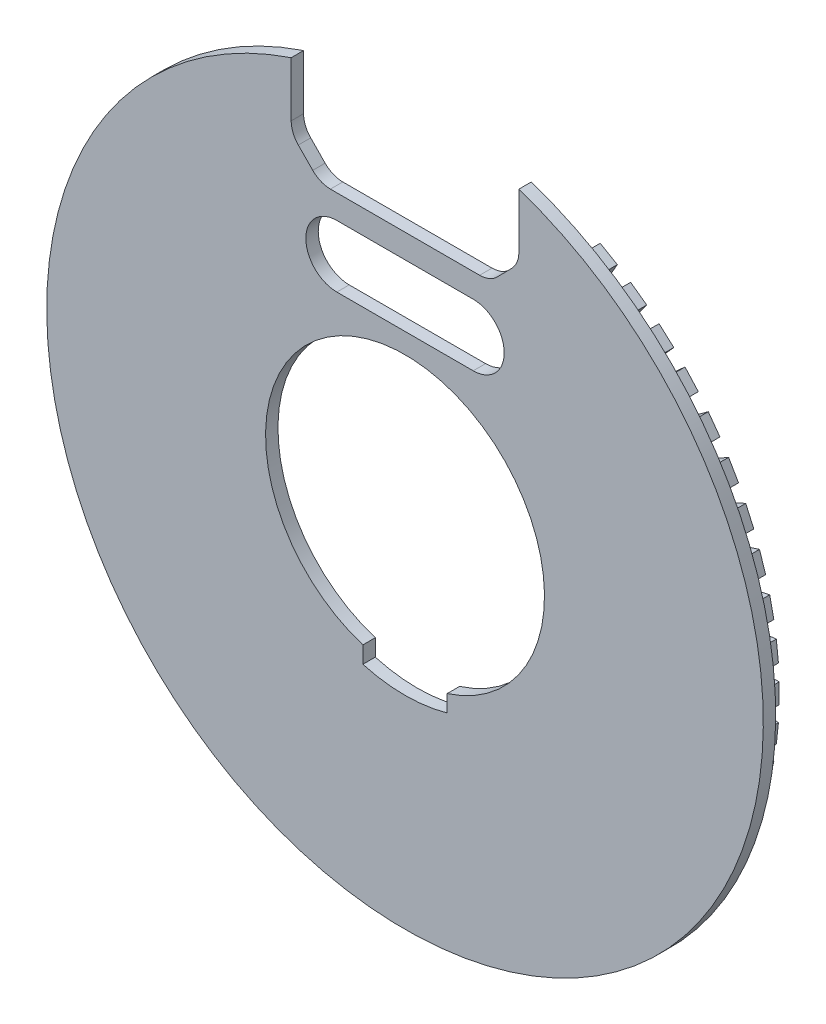
SolidWorks part; units mm, degrees
ref_plane "Front Plane" through (0, 0, 0) normal (0, 0, 1) x (1, 0, 0)
ref_plane "Top Plane" through (0, 0, 0) normal (0, 1, 0) x (1, 0, 0)
ref_plane "Right Plane" through (0, 0, 0) normal (1, 0, 0) x (0, 0, -1)
ref_axis "Axis1" through (0, 0, 54.6575) along (0, 0, -1)
sketch "Sketch1" plane through (0, 0, 0) normal (0, 0, 1) x (1, 0, 0)
  line L12 (20.9871, 19.8336) -> (20.5267, 19.3732)
  line L14 (27.041, 8.0901) -> (27.67, 8.2586)
  line L16 (-27.67, 8.2586) -> (-27.041, 8.0901)
  line L21 (-20.5267, 19.3732) -> (-20.9871, 19.8336)
  line L72 (-4.297, -11.3403) -> (-4.297, -10.3637)
  line L89 (4.297, -11.3403) -> (4.297, -10.3637)
  line L92 (4.297, -11.3403) -> (4.297, -10.3637)
  line L93 (-4.297, -11.3403) -> (-4.297, -10.3637)
  line L100 (-10.7726, 3.134) -> (-10.6892, 3.0858)
  line L101 (-8.017, 7.7142) -> (-8.1004, 7.7623)
  line L102 (-8.1004, -7.7623) -> (-8.017, -7.7142)
  line L103 (-10.6892, -3.0858) -> (-10.7726, -3.134)
  line L104 (10.7726, -3.134) -> (10.6892, -3.0858)
  line L105 (8.017, -7.7142) -> (8.1004, -7.7623)
  line L120 (8.1004, 7.7623) -> (8.017, 7.7142)
  line L121 (10.6892, 3.0858) -> (10.7726, 3.134)
  line L122 (-2.6722, 10.8963) -> (-2.6722, 10.8)
  line L123 (2.6722, 10.8) -> (2.6722, 10.8963)
  line L196 (6.6828, -28.0922) -> (6.5143, -27.4632)
  line L197 (-6.5143, -27.4632) -> (-6.6828, -28.0922)
  line L206 (2.6722, -12.1691) -> (2.6722, -10.8)
  line L207 (-2.6722, -10.8) -> (-2.6722, -12.1691)
  line L210 (27.154, -15.4668) -> (26.9697, -15.2479)
  line L211 (28.01, -13.2402) -> (28.2951, -13.2646)
  line L212 (24.7951, -19.0202) -> (24.6422, -18.7783)
  line L213 (25.9462, -16.931) -> (26.2253, -16.9939)
  line L214 (29.0072, -11.6252) -> (28.7947, -11.4335)
  line L216 (29.552, -9.3029) -> (29.8377, -9.2883)
  line L229 (30.32, -7.5671) -> (30.0834, -7.4061)
  line L230 (30.5435, -5.1923) -> (30.8246, -5.1388)
  line L231 (31.068, -3.3681) -> (30.8117, -3.2408)
  line L232 (30.966, -0.9849) -> (31.2372, -0.8937)
  line L233 (31.2372, 0.8937) -> (30.966, 0.9849)
  line L234 (30.8117, 3.2408) -> (31.068, 3.3681)
  line L235 (30.8246, 5.1388) -> (30.5435, 5.1923)
  line L238 (30.0834, 7.4061) -> (30.32, 7.5671)
  line L239 (29.8377, 9.2883) -> (29.552, 9.3029)
  line L240 (28.7947, 11.4335) -> (29.0072, 11.6252)
  line L241 (-11.3028, 29.1343) -> (-11.2979, 28.8482)
  line L242 (-13.3719, 27.9474) -> (-13.5777, 28.1462)
  line L243 (-15.1646, 27.3239) -> (-15.1208, 27.0411)
  line L244 (-17.0528, 25.8663) -> (-17.2838, 26.0352)
  line L245 (17.2838, 26.0352) -> (17.0528, 25.8663)
  line L246 (15.1208, 27.0411) -> (15.1646, 27.3239)
  line L247 (13.5777, 28.1462) -> (13.3719, 27.9474)
  line L248 (11.2979, 28.8482) -> (11.3028, 29.1343)
  line L249 (26.2253, 16.9939) -> (25.9462, 16.931)
  line L250 (24.6422, 18.7783) -> (24.7951, 19.0202)
  line L251 (28.2951, 13.2646) -> (28.01, 13.2402)
  line L252 (26.9697, 15.2479) -> (27.154, 15.4668)
  line L253 (20.6679, 23.4393) -> (20.4161, 23.3033)
  line L254 (18.6621, 24.7303) -> (18.744, 25.0045)
  line L255 (23.6671, 20.4067) -> (23.3991, 20.3063)
  line L256 (21.8557, 21.9588) -> (21.9742, 22.2193)
  line L257 (-24.7951, 19.0202) -> (-24.6422, 18.7783)
  line L258 (-25.9462, 16.931) -> (-26.2253, 16.9939)
  line L259 (-27.154, 15.4668) -> (-26.9697, 15.2479)
  line L260 (-28.01, 13.2402) -> (-28.2951, 13.2646)
  line L261 (-18.744, 25.0045) -> (-18.6621, 24.7303)
  line L262 (-20.4161, 23.3033) -> (-20.6679, 23.4393)
  line L263 (-21.9742, 22.2193) -> (-21.8557, 21.9588)
  line L264 (-23.3991, 20.3063) -> (-23.6671, 20.4067)
  line L265 (-29.0072, 11.6252) -> (-28.7947, 11.4335)
  line L266 (-29.552, 9.3029) -> (-29.8377, 9.2883)
  line L267 (-30.32, 7.5671) -> (-30.0834, 7.4061)
  line L268 (-30.5435, 5.1923) -> (-30.8246, 5.1388)
  line L269 (-31.068, 3.3681) -> (-30.8117, 3.2408)
  line L270 (-30.966, 0.9849) -> (-31.2372, 0.8937)
  line L271 (-31.2372, -0.8937) -> (-30.966, -0.9849)
  line L272 (-30.8117, -3.2408) -> (-31.068, -3.3681)
  line L273 (-20.6679, -23.4393) -> (-20.4161, -23.3033)
  line L274 (-18.6621, -24.7303) -> (-18.744, -25.0045)
  line L275 (-23.6671, -20.4067) -> (-23.3991, -20.3063)
  line L276 (-21.8557, -21.9588) -> (-21.9742, -22.2193)
  line L277 (-13.5777, -28.1462) -> (-13.3719, -27.9474)
  line L278 (-11.2979, -28.8482) -> (-11.3028, -29.1343)
  line L279 (-17.2838, -26.0352) -> (-17.0528, -25.8663)
  line L280 (-15.1208, -27.0411) -> (-15.1646, -27.3239)
  line L281 (-28.2951, -13.2646) -> (-28.01, -13.2402)
  line L282 (-26.9697, -15.2479) -> (-27.154, -15.4668)
  line L283 (-26.2253, -16.9939) -> (-25.9462, -16.931)
  line L284 (-24.6422, -18.7783) -> (-24.7951, -19.0202)
  line L285 (-29.8377, -9.2883) -> (-29.552, -9.3029)
  line L286 (-28.7947, -11.4335) -> (-29.0072, -11.6252)
  line L287 (-30.8246, -5.1388) -> (-30.5435, -5.1923)
  line L288 (-30.0834, -7.4061) -> (-30.32, -7.5671)
  line L289 (15.1646, -27.3239) -> (15.1208, -27.0411)
  line L290 (17.0528, -25.8663) -> (17.2838, -26.0352)
  line L291 (11.3028, -29.1343) -> (11.2979, -28.8482)
  line L292 (13.3719, -27.9474) -> (13.5777, -28.1462)
  line L293 (21.9742, -22.2193) -> (21.8557, -21.9588)
  line L294 (23.3991, -20.3063) -> (23.6671, -20.4067)
  line L295 (18.744, -25.0045) -> (18.6621, -24.7303)
  line L296 (20.4161, -23.3033) -> (20.6679, -23.4393)
  line L297 (-9.6186, -29.7329) -> (-9.4418, -29.5079)
  line L298 (-7.2645, -30.1179) -> (-7.2304, -30.402)
  line L299 (7.2304, -30.402) -> (7.2645, -30.1179)
  line L300 (9.4418, -29.5079) -> (9.6186, -29.7329)
  line L301 (-7.0878, 20.754) -> (-8.2524, 21.9387)
  line L302 (8.2524, 21.9387) -> (7.0878, 20.754)
  line L303 (-8.6826, 26.4576) -> (-8.6826, 22.9901)
  line L304 (8.6826, 26.4576) -> (8.6826, 22.9901)
  line L305 (4.4477, 24.65) -> (4.4477, 31.5861)
  line L306 (-4.4477, 31.5861) -> (-4.4477, 24.65)
  line L307 (4.5426, 32.95) -> (4.5426, 31.81)
  line L308 (-4.5426, 31.81) -> (-4.5426, 32.95)
  line L309 (-6.1155, 33.25) -> (-5.0016, 33.25)
  line L310 (5.0016, 33.25) -> (6.1155, 33.25)
  line L311 (6.0182, 20.3056) -> (-6.0182, 20.3056)
  line L312 (6.0182, 20.3056) -> (-6.0182, 20.3056)
  line L313 (5.0016, 33.25) -> (6.1155, 33.25)
  line L314 (-6.1155, 33.25) -> (-5.0016, 33.25)
  line L315 (-4.5426, 31.81) -> (-4.5426, 32.95)
  line L316 (4.5426, 32.95) -> (4.5426, 31.81)
  line L317 (-4.4477, 31.5861) -> (-4.4477, 24.65)
  line L318 (4.4477, 24.65) -> (4.4477, 31.5861)
  line L319 (8.6826, 26.4576) -> (8.6826, 22.9901)
  line L320 (-8.6826, 26.4576) -> (-8.6826, 22.9901)
  line L321 (8.2524, 21.9387) -> (7.0878, 20.754)
  line L322 (-7.0878, 20.754) -> (-8.2524, 21.9387)
  line L323 (9.4418, -29.5079) -> (9.6186, -29.7329)
  line L324 (7.2304, -30.402) -> (7.2645, -30.1179)
  line L325 (-7.2645, -30.1179) -> (-7.2304, -30.402)
  line L326 (-9.6186, -29.7329) -> (-9.4418, -29.5079)
  line L327 (20.4161, -23.3033) -> (20.6679, -23.4393)
  line L328 (18.744, -25.0045) -> (18.6621, -24.7303)
  line L329 (23.3991, -20.3063) -> (23.6671, -20.4067)
  line L330 (21.9742, -22.2193) -> (21.8557, -21.9588)
  line L331 (13.3719, -27.9474) -> (13.5777, -28.1462)
  line L332 (11.3028, -29.1343) -> (11.2979, -28.8482)
  line L333 (17.0528, -25.8663) -> (17.2838, -26.0352)
  line L334 (15.1646, -27.3239) -> (15.1208, -27.0411)
  line L335 (-30.0834, -7.4061) -> (-30.32, -7.5671)
  line L336 (-30.8246, -5.1388) -> (-30.5435, -5.1923)
  line L337 (-28.7947, -11.4335) -> (-29.0072, -11.6252)
  line L338 (-29.8377, -9.2883) -> (-29.552, -9.3029)
  line L339 (-24.6422, -18.7783) -> (-24.7951, -19.0202)
  line L340 (-26.2253, -16.9939) -> (-25.9462, -16.931)
  line L341 (-26.9697, -15.2479) -> (-27.154, -15.4668)
  line L342 (-28.2951, -13.2646) -> (-28.01, -13.2402)
  line L343 (-15.1208, -27.0411) -> (-15.1646, -27.3239)
  line L344 (-17.2838, -26.0352) -> (-17.0528, -25.8663)
  line L345 (-11.2979, -28.8482) -> (-11.3028, -29.1343)
  line L346 (-13.5777, -28.1462) -> (-13.3719, -27.9474)
  line L347 (-21.8557, -21.9588) -> (-21.9742, -22.2193)
  line L348 (-23.6671, -20.4067) -> (-23.3991, -20.3063)
  line L349 (-18.6621, -24.7303) -> (-18.744, -25.0045)
  line L350 (-20.6679, -23.4393) -> (-20.4161, -23.3033)
  line L351 (-30.8117, -3.2408) -> (-31.068, -3.3681)
  line L352 (-31.2372, -0.8937) -> (-30.966, -0.9849)
  line L353 (-30.966, 0.9849) -> (-31.2372, 0.8937)
  line L354 (-31.068, 3.3681) -> (-30.8117, 3.2408)
  line L355 (-30.5435, 5.1923) -> (-30.8246, 5.1388)
  line L356 (-30.32, 7.5671) -> (-30.0834, 7.4061)
  line L357 (-29.552, 9.3029) -> (-29.8377, 9.2883)
  line L358 (-29.0072, 11.6252) -> (-28.7947, 11.4335)
  line L359 (-23.3991, 20.3063) -> (-23.6671, 20.4067)
  line L360 (-21.9742, 22.2193) -> (-21.8557, 21.9588)
  line L361 (-20.4161, 23.3033) -> (-20.6679, 23.4393)
  line L362 (-18.744, 25.0045) -> (-18.6621, 24.7303)
  line L363 (-28.01, 13.2402) -> (-28.2951, 13.2646)
  line L364 (-27.154, 15.4668) -> (-26.9697, 15.2479)
  line L365 (-25.9462, 16.931) -> (-26.2253, 16.9939)
  line L366 (-24.7951, 19.0202) -> (-24.6422, 18.7783)
  line L367 (21.8557, 21.9588) -> (21.9742, 22.2193)
  line L368 (23.6671, 20.4067) -> (23.3991, 20.3063)
  line L369 (18.6621, 24.7303) -> (18.744, 25.0045)
  line L370 (20.6679, 23.4393) -> (20.4161, 23.3033)
  line L371 (26.9697, 15.2479) -> (27.154, 15.4668)
  line L372 (28.2951, 13.2646) -> (28.01, 13.2402)
  line L373 (24.6422, 18.7783) -> (24.7951, 19.0202)
  line L374 (26.2253, 16.9939) -> (25.9462, 16.931)
  line L375 (11.2979, 28.8482) -> (11.3028, 29.1343)
  line L376 (13.5777, 28.1462) -> (13.3719, 27.9474)
  line L377 (15.1208, 27.0411) -> (15.1646, 27.3239)
  line L378 (17.2838, 26.0352) -> (17.0528, 25.8663)
  line L379 (-17.0528, 25.8663) -> (-17.2838, 26.0352)
  line L380 (-15.1646, 27.3239) -> (-15.1208, 27.0411)
  line L381 (-13.3719, 27.9474) -> (-13.5777, 28.1462)
  line L382 (-11.3028, 29.1343) -> (-11.2979, 28.8482)
  line L383 (28.7947, 11.4335) -> (29.0072, 11.6252)
  line L384 (29.8377, 9.2883) -> (29.552, 9.3029)
  line L385 (30.0834, 7.4061) -> (30.32, 7.5671)
  line L386 (30.8246, 5.1388) -> (30.5435, 5.1923)
  line L387 (30.8117, 3.2408) -> (31.068, 3.3681)
  line L388 (31.2372, 0.8937) -> (30.966, 0.9849)
  line L389 (30.966, -0.9849) -> (31.2372, -0.8937)
  line L390 (31.068, -3.3681) -> (30.8117, -3.2408)
  line L391 (30.5435, -5.1923) -> (30.8246, -5.1388)
  line L392 (30.32, -7.5671) -> (30.0834, -7.4061)
  line L393 (29.552, -9.3029) -> (29.8377, -9.2883)
  line L394 (29.0072, -11.6252) -> (28.7947, -11.4335)
  line L395 (25.9462, -16.931) -> (26.2253, -16.9939)
  line L396 (24.7951, -19.0202) -> (24.6422, -18.7783)
  line L397 (28.01, -13.2402) -> (28.2951, -13.2646)
  line L398 (27.154, -15.4668) -> (26.9697, -15.2479)
  line L420 (-2.6722, -10.8) -> (-2.6722, -12.1691)
  line L421 (2.6722, -12.1691) -> (2.6722, -10.8)
  line L430 (2.6722, 10.8) -> (2.6722, 10.8963)
  line L431 (-2.6722, 10.8963) -> (-2.6722, 10.8)
  line L432 (10.6892, 3.0858) -> (10.7726, 3.134)
  line L433 (8.1004, 7.7623) -> (8.017, 7.7142)
  line L434 (8.017, -7.7142) -> (8.1004, -7.7623)
  line L435 (10.7726, -3.134) -> (10.6892, -3.0858)
  line L436 (-10.6892, -3.0858) -> (-10.7726, -3.134)
  line L437 (-8.1004, -7.7623) -> (-8.017, -7.7142)
  line L438 (-8.017, 7.7142) -> (-8.1004, 7.7623)
  line L439 (-10.7726, 3.134) -> (-10.6892, 3.0858)
  line L510 (-6.5143, -27.4632) -> (-6.6828, -28.0922)
  line L511 (6.6828, -28.0922) -> (6.5143, -27.4632)
  line L512 (-20.5267, 19.3732) -> (-20.9871, 19.8336)
  line L513 (-27.67, 8.2586) -> (-27.041, 8.0901)
  line L514 (27.041, 8.0901) -> (27.67, 8.2586)
  line L515 (20.9871, 19.8336) -> (20.5267, 19.3732)
  arc A18 (27.67, 8.2586) -> (20.9871, 19.8336) centre (0, 0) ccw
  arc A80 (-3.9559, -11.8144) -> (-2.6722, -12.1691) centre (0, 0) ccw
  arc A82 (-3.9559, -11.8144) -> (-2.6722, -12.1691) centre (0, 0) ccw
  arc A149 (27.041, 8.0901) -> (20.5267, 19.3732) centre (0, 0) ccw
  arc A153 (-20.9871, 19.8336) -> (-27.67, 8.2586) centre (0, 0) ccw
  arc A162 (-20.5267, 19.3732) -> (-27.041, 8.0901) centre (0, 0) ccw
  arc A163 (-6.6828, -28.0922) -> (6.6828, -28.0922) centre (0, 0) ccw
  arc A164 (-6.5143, -27.4632) -> (6.5143, -27.4632) centre (0, 0) ccw
  arc A211 (2.6722, -10.8) -> (-2.6722, -10.8) centre (0, -10.8) ccw
  arc A217 (2.6722, -12.1691) -> (3.9559, -11.8144) centre (0, 0) ccw
  arc A225 (2.6722, -12.1691) -> (3.9559, -11.8144) centre (0, 0) ccw
  arc A226 (2.6722, -10.8) -> (-2.6722, -10.8) centre (0, -10.8) ccw
  arc A257 (-10.6892, 3.0858) -> (-8.017, 7.7142) centre (-9.3531, 5.4) ccw
  arc A258 (-8.017, -7.7142) -> (-10.6892, -3.0858) centre (-9.3531, -5.4) ccw
  arc A260 (10.6892, -3.0858) -> (8.017, -7.7142) centre (9.3531, -5.4) ccw
  arc A261 (8.017, 7.7142) -> (10.6892, 3.0858) centre (9.3531, 5.4) ccw
  arc A262 (-2.6722, 10.8) -> (2.6722, 10.8) centre (0, 10.8) ccw
  arc A263 (26.9697, -15.2479) -> (28.01, -13.2402) centre (0, 0) ccw
  arc A264 (24.6422, -18.7783) -> (25.9462, -16.931) centre (0, 0) ccw
  arc A265 (28.7947, -11.4335) -> (29.552, -9.3029) centre (0, 0) ccw
  arc A266 (30.0834, -7.4061) -> (30.5435, -5.1923) centre (0, 0) ccw
  arc A267 (30.8117, -3.2408) -> (30.966, -0.9849) centre (0, 0) ccw
  arc A268 (30.966, 0.9849) -> (30.8117, 3.2408) centre (0, 0) ccw
  arc A269 (30.5435, 5.1923) -> (30.0834, 7.4061) centre (0, 0) ccw
  arc A270 (29.552, 9.3029) -> (28.7947, 11.4335) centre (0, 0) ccw
  arc A271 (-11.2979, 28.8482) -> (-13.3719, 27.9474) centre (0, 0) ccw
  arc A272 (-15.1208, 27.0411) -> (-17.0528, 25.8663) centre (0, 0) ccw
  arc A273 (17.0528, 25.8663) -> (15.1208, 27.0411) centre (0, 0) ccw
  arc A274 (13.3719, 27.9474) -> (11.2979, 28.8482) centre (0, 0) ccw
  arc A275 (25.9462, 16.931) -> (24.6422, 18.7783) centre (0, 0) ccw
  arc A276 (28.01, 13.2402) -> (26.9697, 15.2479) centre (0, 0) ccw
  arc A277 (20.4161, 23.3033) -> (18.6621, 24.7303) centre (0, 0) ccw
  arc A278 (23.3991, 20.3063) -> (21.8557, 21.9588) centre (0, 0) ccw
  arc A279 (-24.6422, 18.7783) -> (-25.9462, 16.931) centre (0, 0) ccw
  arc A280 (-26.9697, 15.2479) -> (-28.01, 13.2402) centre (0, 0) ccw
  arc A281 (-18.6621, 24.7303) -> (-20.4161, 23.3033) centre (0, 0) ccw
  arc A283 (-21.8557, 21.9588) -> (-23.3991, 20.3063) centre (0, 0) ccw
  arc A284 (-28.7947, 11.4335) -> (-29.552, 9.3029) centre (0, 0) ccw
  arc A285 (-30.0834, 7.4061) -> (-30.5435, 5.1923) centre (0, 0) ccw
  arc A286 (-30.8117, 3.2408) -> (-30.966, 0.9849) centre (0, 0) ccw
  arc A287 (-30.966, -0.9849) -> (-30.8117, -3.2408) centre (0, 0) ccw
  arc A288 (-20.4161, -23.3033) -> (-18.6621, -24.7303) centre (0, 0) ccw
  arc A289 (-23.3991, -20.3063) -> (-21.8557, -21.9588) centre (0, 0) ccw
  arc A290 (-13.3719, -27.9474) -> (-11.2979, -28.8482) centre (0, 0) ccw
  arc A291 (-17.0528, -25.8663) -> (-15.1208, -27.0411) centre (0, 0) ccw
  arc A292 (-28.01, -13.2402) -> (-26.9697, -15.2479) centre (0, 0) ccw
  arc A293 (-25.9462, -16.931) -> (-24.6422, -18.7783) centre (0, 0) ccw
  arc A294 (-29.552, -9.3029) -> (-28.7947, -11.4335) centre (0, 0) ccw
  arc A295 (-30.5435, -5.1923) -> (-30.0834, -7.4061) centre (0, 0) ccw
  arc A296 (15.1208, -27.0411) -> (17.0528, -25.8663) centre (0, 0) ccw
  arc A297 (11.2979, -28.8482) -> (13.3719, -27.9474) centre (0, 0) ccw
  arc A298 (21.8557, -21.9588) -> (23.3991, -20.3063) centre (0, 0) ccw
  arc A299 (18.6621, -24.7303) -> (20.4161, -23.3033) centre (0, 0) ccw
  arc A300 (-9.4418, -29.5079) -> (-7.2645, -30.1179) centre (0, 0) ccw
  arc A301 (7.2645, -30.1179) -> (9.4418, -29.5079) centre (0, 0) ccw
  circle A302 centre (0, 0) radius 5
  arc A385 (9.6186, -29.7329) -> (11.3028, -29.1343) centre (0, 0) ccw
  arc A389 (7.2598, -28.2558) -> (28.1002, 7.8407) centre (0, 0) ccw
  arc A390 (-7.2304, -30.402) -> (7.2304, -30.402) centre (0, 0) ccw
  arc A391 (20.6679, -23.4393) -> (21.9742, -22.2193) centre (0, 0) ccw
  arc A392 (23.6671, -20.4067) -> (24.7951, -19.0202) centre (0, 0) ccw
  arc A393 (13.5777, -28.1462) -> (15.1646, -27.3239) centre (0, 0) ccw
  arc A394 (17.2838, -26.0352) -> (18.744, -25.0045) centre (0, 0) ccw
  arc A395 (-30.32, -7.5671) -> (-29.8377, -9.2883) centre (0, 0) ccw
  arc A396 (-29.0072, -11.6252) -> (-28.2951, -13.2646) centre (0, 0) ccw
  arc A397 (-24.7951, -19.0202) -> (-23.6671, -20.4067) centre (0, 0) ccw
  arc A398 (-27.154, -15.4668) -> (-26.2253, -16.9939) centre (0, 0) ccw
  arc A399 (-15.1646, -27.3239) -> (-13.5777, -28.1462) centre (0, 0) ccw
  arc A400 (-11.3028, -29.1343) -> (-9.6186, -29.7329) centre (0, 0) ccw
  arc A401 (-21.9742, -22.2193) -> (-20.6679, -23.4393) centre (0, 0) ccw
  arc A402 (-18.744, -25.0045) -> (-17.2838, -26.0352) centre (0, 0) ccw
  arc A403 (-31.068, -3.3681) -> (-30.8246, -5.1388) centre (0, 0) ccw
  arc A404 (-31.2372, 0.8937) -> (-31.2372, -0.8937) centre (0, 0) ccw
  arc A405 (-30.8246, 5.1388) -> (-31.068, 3.3681) centre (0, 0) ccw
  arc A406 (-29.8377, 9.2883) -> (-30.32, 7.5671) centre (0, 0) ccw
  arc A407 (-23.6671, 20.4067) -> (-24.7951, 19.0202) centre (0, 0) ccw
  arc A408 (-20.6679, 23.4393) -> (-21.9742, 22.2193) centre (0, 0) ccw
  arc A409 (-28.2951, 13.2646) -> (-29.0072, 11.6252) centre (0, 0) ccw
  arc A410 (-26.2253, 16.9939) -> (-27.154, 15.4668) centre (0, 0) ccw
  arc A411 (21.9742, 22.2193) -> (20.6679, 23.4393) centre (0, 0) ccw
  arc A412 (18.744, 25.0045) -> (17.2838, 26.0352) centre (0, 0) ccw
  arc A413 (27.154, 15.4668) -> (26.2253, 16.9939) centre (0, 0) ccw
  arc A414 (24.7951, 19.0202) -> (23.6671, 20.4067) centre (0, 0) ccw
  arc A415 (-9.2957, 29.8354) -> (-11.3028, 29.1343) centre (0, 0) ccw
  arc A416 (11.3028, 29.1343) -> (9.2957, 29.8354) centre (0, 0) ccw
  arc A417 (15.1646, 27.3239) -> (13.5777, 28.1462) centre (0, 0) ccw
  arc A418 (-17.2838, 26.0352) -> (-18.744, 25.0045) centre (0, 0) ccw
  arc A419 (-13.5777, 28.1462) -> (-15.1646, 27.3239) centre (0, 0) ccw
  arc A420 (29.0072, 11.6252) -> (28.2951, 13.2646) centre (0, 0) ccw
  arc A421 (30.32, 7.5671) -> (29.8377, 9.2883) centre (0, 0) ccw
  arc A422 (31.068, 3.3681) -> (30.8246, 5.1388) centre (0, 0) ccw
  arc A423 (31.2372, -0.8937) -> (31.2372, 0.8937) centre (0, 0) ccw
  arc A424 (30.8246, -5.1388) -> (31.068, -3.3681) centre (0, 0) ccw
  arc A425 (29.8377, -9.2883) -> (30.32, -7.5671) centre (0, 0) ccw
  arc A426 (26.2253, -16.9939) -> (27.154, -15.4668) centre (0, 0) ccw
  arc A427 (28.2951, -13.2646) -> (29.0072, -11.6252) centre (0, 0) ccw
  arc A439 (10.7726, -3.134) -> (10.7726, 3.134) centre (0, 0) ccw
  arc A440 (10.7726, -3.134) -> (10.7726, 3.134) centre (0, 0) ccw
  arc A452 (28.2951, -13.2646) -> (29.0072, -11.6252) centre (0, 0) ccw
  arc A453 (26.2253, -16.9939) -> (27.154, -15.4668) centre (0, 0) ccw
  arc A454 (29.8377, -9.2883) -> (30.32, -7.5671) centre (0, 0) ccw
  arc A455 (30.8246, -5.1388) -> (31.068, -3.3681) centre (0, 0) ccw
  arc A456 (31.2372, -0.8937) -> (31.2372, 0.8937) centre (0, 0) ccw
  arc A457 (31.068, 3.3681) -> (30.8246, 5.1388) centre (0, 0) ccw
  arc A458 (30.32, 7.5671) -> (29.8377, 9.2883) centre (0, 0) ccw
  arc A459 (29.0072, 11.6252) -> (28.2951, 13.2646) centre (0, 0) ccw
  arc A460 (-13.5777, 28.1462) -> (-15.1646, 27.3239) centre (0, 0) ccw
  arc A461 (-17.2838, 26.0352) -> (-18.744, 25.0045) centre (0, 0) ccw
  arc A462 (15.1646, 27.3239) -> (13.5777, 28.1462) centre (0, 0) ccw
  arc A463 (11.3028, 29.1343) -> (9.2957, 29.8354) centre (0, 0) ccw
  arc A464 (-9.2957, 29.8354) -> (-11.3028, 29.1343) centre (0, 0) ccw
  arc A465 (24.7951, 19.0202) -> (23.6671, 20.4067) centre (0, 0) ccw
  arc A466 (27.154, 15.4668) -> (26.2253, 16.9939) centre (0, 0) ccw
  arc A467 (18.744, 25.0045) -> (17.2838, 26.0352) centre (0, 0) ccw
  arc A468 (21.9742, 22.2193) -> (20.6679, 23.4393) centre (0, 0) ccw
  arc A469 (-26.2253, 16.9939) -> (-27.154, 15.4668) centre (0, 0) ccw
  arc A470 (-28.2951, 13.2646) -> (-29.0072, 11.6252) centre (0, 0) ccw
  arc A471 (-20.6679, 23.4393) -> (-21.9742, 22.2193) centre (0, 0) ccw
  arc A472 (-23.6671, 20.4067) -> (-24.7951, 19.0202) centre (0, 0) ccw
  arc A473 (-29.8377, 9.2883) -> (-30.32, 7.5671) centre (0, 0) ccw
  arc A474 (-30.8246, 5.1388) -> (-31.068, 3.3681) centre (0, 0) ccw
  arc A475 (-31.2372, 0.8937) -> (-31.2372, -0.8937) centre (0, 0) ccw
  arc A476 (-31.068, -3.3681) -> (-30.8246, -5.1388) centre (0, 0) ccw
  arc A477 (-18.744, -25.0045) -> (-17.2838, -26.0352) centre (0, 0) ccw
  arc A478 (-21.9742, -22.2193) -> (-20.6679, -23.4393) centre (0, 0) ccw
  arc A479 (-11.3028, -29.1343) -> (-9.6186, -29.7329) centre (0, 0) ccw
  arc A480 (-15.1646, -27.3239) -> (-13.5777, -28.1462) centre (0, 0) ccw
  arc A481 (-27.154, -15.4668) -> (-26.2253, -16.9939) centre (0, 0) ccw
  arc A482 (-24.7951, -19.0202) -> (-23.6671, -20.4067) centre (0, 0) ccw
  arc A483 (-29.0072, -11.6252) -> (-28.2951, -13.2646) centre (0, 0) ccw
  arc A484 (-30.32, -7.5671) -> (-29.8377, -9.2883) centre (0, 0) ccw
  arc A485 (17.2838, -26.0352) -> (18.744, -25.0045) centre (0, 0) ccw
  arc A486 (13.5777, -28.1462) -> (15.1646, -27.3239) centre (0, 0) ccw
  arc A487 (23.6671, -20.4067) -> (24.7951, -19.0202) centre (0, 0) ccw
  arc A488 (20.6679, -23.4393) -> (21.9742, -22.2193) centre (0, 0) ccw
  arc A489 (-7.2304, -30.402) -> (7.2304, -30.402) centre (0, 0) ccw
  arc A490 (7.2598, -28.2558) -> (28.1002, 7.8407) centre (0, 0) ccw
  arc A494 (9.6186, -29.7329) -> (11.3028, -29.1343) centre (0, 0) ccw
  circle A495 centre (0, 0) radius 5
  arc A496 (7.2645, -30.1179) -> (9.4418, -29.5079) centre (0, 0) ccw
  arc A497 (-9.4418, -29.5079) -> (-7.2645, -30.1179) centre (0, 0) ccw
  arc A498 (18.6621, -24.7303) -> (20.4161, -23.3033) centre (0, 0) ccw
  arc A499 (21.8557, -21.9588) -> (23.3991, -20.3063) centre (0, 0) ccw
  arc A500 (11.2979, -28.8482) -> (13.3719, -27.9474) centre (0, 0) ccw
  arc A501 (15.1208, -27.0411) -> (17.0528, -25.8663) centre (0, 0) ccw
  arc A502 (-30.5435, -5.1923) -> (-30.0834, -7.4061) centre (0, 0) ccw
  arc A503 (-29.552, -9.3029) -> (-28.7947, -11.4335) centre (0, 0) ccw
  arc A504 (-25.9462, -16.931) -> (-24.6422, -18.7783) centre (0, 0) ccw
  arc A505 (-28.01, -13.2402) -> (-26.9697, -15.2479) centre (0, 0) ccw
  arc A506 (-17.0528, -25.8663) -> (-15.1208, -27.0411) centre (0, 0) ccw
  arc A507 (-13.3719, -27.9474) -> (-11.2979, -28.8482) centre (0, 0) ccw
  arc A508 (-23.3991, -20.3063) -> (-21.8557, -21.9588) centre (0, 0) ccw
  arc A509 (-20.4161, -23.3033) -> (-18.6621, -24.7303) centre (0, 0) ccw
  arc A510 (-30.966, -0.9849) -> (-30.8117, -3.2408) centre (0, 0) ccw
  arc A511 (-30.8117, 3.2408) -> (-30.966, 0.9849) centre (0, 0) ccw
  arc A512 (-30.0834, 7.4061) -> (-30.5435, 5.1923) centre (0, 0) ccw
  arc A513 (-28.7947, 11.4335) -> (-29.552, 9.3029) centre (0, 0) ccw
  arc A514 (-21.8557, 21.9588) -> (-23.3991, 20.3063) centre (0, 0) ccw
  arc A515 (-18.6621, 24.7303) -> (-20.4161, 23.3033) centre (0, 0) ccw
  arc A516 (-26.9697, 15.2479) -> (-28.01, 13.2402) centre (0, 0) ccw
  arc A517 (-24.6422, 18.7783) -> (-25.9462, 16.931) centre (0, 0) ccw
  arc A518 (23.3991, 20.3063) -> (21.8557, 21.9588) centre (0, 0) ccw
  arc A519 (20.4161, 23.3033) -> (18.6621, 24.7303) centre (0, 0) ccw
  arc A520 (28.01, 13.2402) -> (26.9697, 15.2479) centre (0, 0) ccw
  arc A521 (25.9462, 16.931) -> (24.6422, 18.7783) centre (0, 0) ccw
  arc A522 (13.3719, 27.9474) -> (11.2979, 28.8482) centre (0, 0) ccw
  arc A523 (17.0528, 25.8663) -> (15.1208, 27.0411) centre (0, 0) ccw
  arc A524 (-15.1208, 27.0411) -> (-17.0528, 25.8663) centre (0, 0) ccw
  arc A525 (-11.2979, 28.8482) -> (-13.3719, 27.9474) centre (0, 0) ccw
  arc A526 (29.552, 9.3029) -> (28.7947, 11.4335) centre (0, 0) ccw
  arc A527 (30.5435, 5.1923) -> (30.0834, 7.4061) centre (0, 0) ccw
  arc A528 (30.966, 0.9849) -> (30.8117, 3.2408) centre (0, 0) ccw
  arc A529 (30.8117, -3.2408) -> (30.966, -0.9849) centre (0, 0) ccw
  arc A530 (30.0834, -7.4061) -> (30.5435, -5.1923) centre (0, 0) ccw
  arc A531 (28.7947, -11.4335) -> (29.552, -9.3029) centre (0, 0) ccw
  arc A532 (24.6422, -18.7783) -> (25.9462, -16.931) centre (0, 0) ccw
  arc A533 (26.9697, -15.2479) -> (28.01, -13.2402) centre (0, 0) ccw
  arc A569 (20.8403, 20.4151) -> (10.0262, 27.3965) centre (0, 0) ccw
  arc A570 (-10.0262, 27.3965) -> (-20.8403, 20.4151) centre (0, 0) ccw
  arc A571 (-28.1002, 7.8407) -> (-7.2598, -28.2558) centre (0, 0) ccw
  arc A617 (4.297, -10.3637) -> (8.1004, -7.7623) centre (0, 0) ccw
  arc A618 (-8.1004, -7.7623) -> (-4.297, -10.3637) centre (0, 0) ccw
  arc A619 (-10.7726, 3.134) -> (-10.7726, -3.134) centre (0, 0) ccw
  arc A620 (-2.6722, 10.8963) -> (-8.1004, 7.7623) centre (0, 0) ccw
  arc A621 (8.1004, 7.7623) -> (2.6722, 10.8963) centre (0, 0) ccw
  arc A623 (8.1004, 7.7623) -> (2.6722, 10.8963) centre (0, 0) ccw
  arc A624 (-2.6722, 10.8963) -> (-8.1004, 7.7623) centre (0, 0) ccw
  arc A625 (-10.7726, 3.134) -> (-10.7726, -3.134) centre (0, 0) ccw
  arc A626 (-8.1004, -7.7623) -> (-4.297, -10.3637) centre (0, 0) ccw
  arc A627 (4.297, -10.3637) -> (8.1004, -7.7623) centre (0, 0) ccw
  arc A634 (-28.1002, 7.8407) -> (-7.2598, -28.2558) centre (0, 0) ccw
  arc A635 (-10.0262, 27.3965) -> (-20.8403, 20.4151) centre (0, 0) ccw
  arc A636 (20.8403, 20.4151) -> (10.0262, 27.3965) centre (0, 0) ccw
  arc A637 (-2.6722, 10.8) -> (2.6722, 10.8) centre (0, 10.8) ccw
  arc A638 (8.017, 7.7142) -> (10.6892, 3.0858) centre (9.3531, 5.4) ccw
  arc A639 (10.6892, -3.0858) -> (8.017, -7.7142) centre (9.3531, -5.4) ccw
  arc A641 (-8.017, -7.7142) -> (-10.6892, -3.0858) centre (-9.3531, -5.4) ccw
  arc A642 (-10.6892, 3.0858) -> (-8.017, 7.7142) centre (-9.3531, 5.4) ccw
  arc A649 (-6.5143, -27.4632) -> (6.5143, -27.4632) centre (0, 0) ccw
  arc A650 (-6.6828, -28.0922) -> (6.6828, -28.0922) centre (0, 0) ccw
  arc A651 (-20.5267, 19.3732) -> (-27.041, 8.0901) centre (0, 0) ccw
  arc A652 (-20.9871, 19.8336) -> (-27.67, 8.2586) centre (0, 0) ccw
  arc A653 (27.041, 8.0901) -> (20.5267, 19.3732) centre (0, 0) ccw
  arc A654 (27.67, 8.2586) -> (20.9871, 19.8336) centre (0, 0) ccw
  spline S0 degree 3 poles (217.1708, -960.1221) (0.3585, 21.5668) (19.7515, 22.0744) (20.904, 20.333) (20.9316, 20.2807) (20.9557, 20.217) (20.9798, 20.1169) (21.2098, 18.0413) (14.5456, 10.7699) (290.4125, -943.1783) knots -10.272576 -10.272576 -10.272576 -10.272576 0.08598 0.16951 0.250206 0.373376 0.499593 0.749781 11.649577 11.649577 11.649577 11.649577 only from (20.8403, 20.4151) to (20.9871, 19.8336)
  spline S1 degree 3 poles (-641.3261, 751.5245) (17.5257, 6.3432) (26.4948, 9.2136) (27.9115, 8.1107) (27.9861, 8.0398) (28.0345, 7.9804) (29.4042, 5.7225) (12.6294, -13.5109) (-867.364, 452.971) knots -9.335309 -9.335309 -9.335309 -9.335309 0.250262 0.500493 0.625814 0.749918 0.872459 13.776337 13.776337 13.776337 13.776337 only from (27.67, 8.2586) to (28.1002, 7.8407)
  spline S2 degree 3 poles (722.7786, 668.2786) (-18.8597, -10.4704) (-28.9926, 6.0684) (-28.0609, 7.9369) (-28.0293, 7.9869) (-27.9862, 8.0397) (-27.9117, 8.1106) (-26.2291, 9.3476) (-16.5998, 7.2119) (671.6119, 723.0956) knots -10.271295 -10.271295 -10.271295 -10.271295 0.08598 0.16951 0.250206 0.373376 0.499593 0.749781 11.649586 11.649586 11.649586 11.649586 only from (-28.1002, 7.8407) to (-27.67, 8.2586)
  spline S3 degree 3 poles (-194.2461, -965.0417) (-15.85, 10.1186) (-21.1863, 18.2876) (-20.9799, 20.1167) (-20.9557, 20.2168) (-20.9285, 20.2884) (-19.658, 22.6033) (5.3819, 17.6954) (41.1497, -977.661) knots -9.785956 -9.785956 -9.785956 -9.785956 0.250262 0.500493 0.625814 0.749918 0.872459 13.774961 13.774961 13.774961 13.774961 only from (-20.9871, 19.8336) to (-20.8403, 20.4151)
  spline S4 degree 3 poles (-939.8997, 292.5025) (18.496, -11.1037) (9.2408, -28.1425) (7.1569, -28.2699) (7.0978, -28.2676) (7.0306, -28.2566) (6.9318, -28.2275) (5.0889, -27.4417) (4.6867, -19.1454) (-972.1627, 176.4034) knots -10.270415 -10.270415 -10.270415 -10.270415 0.08598 0.16951 0.250206 0.373376 0.499593 0.749781 10.939379 10.939379 10.939379 10.939379 only from (7.2598, -28.2558) to (6.6828, -28.0922)
  spline S5 degree 3 poles (954.8747, 246.5088) (-4.2702, -19.9838) (-5.2931, -27.5434) (-6.9316, -28.2274) (-7.0304, -28.2566) (-7.106, -28.2688) (-9.7459, -28.326) (-18.0144, -4.1897) (825.8713, 524.8007) knots -9.054356 -9.054356 -9.054356 -9.054356 0.250262 0.500493 0.625814 0.749918 0.872459 13.774648 13.774648 13.774648 13.774648 only from (-6.6828, -28.0922) to (-7.2598, -28.2558)
  spline S6 degree 3 poles (-6.5795, 32.9) (-6.5826, 32.8593) (-6.5907, 32.7795) (-6.6029, 32.6996) (-6.6097, 32.6605) knots 0 0 0 0 0.504523 1 1 1 1
  spline S7 degree 3 poles (6.6097, 32.6605) (6.6029, 32.6997) (6.5907, 32.7796) (6.5826, 32.8593) (6.5795, 32.9) knots 0 0 0 0 0.495803 1 1 1 1
  spline S8 degree 3 poles (789.8086, -620.0396) (-8.5623, 4.2485) (-2.1267, -12.9005) (-4.0858, -11.7506) (-4.1441, -11.703) (-4.1956, -11.6454) (-4.2388, -11.579) (-4.2714, -11.5048) (-4.7779, -9.6516) (5.4195, 8.0682) (375.7299, -936.3054) knots -9.649477 -9.649477 -9.649477 -9.649477 0.114188 0.231459 0.351818 0.475266 0.601806 0.731441 0.864171 10.72703 10.72703 10.72703 10.72703 only from (-3.9559, -11.8144) to (-4.297, -11.3403)
  spline S9 degree 3 poles (-304.1195, -962.5915) (-3.1528, 6.3087) (4.6349, -9.8467) (4.2804, -11.4733) (4.259, -11.5353) (4.2301, -11.5928) (4.1949, -11.6452) (4.1543, -11.6919) (4.1092, -11.7324) (4.0606, -11.7664) (2.389, -12.6543) (9.7092, 0.2479) (-840.6659, -547.1402) knots -8.481812 -8.481812 -8.481812 -8.481812 0.108918 0.215851 0.3208 0.423767 0.524752 0.623757 0.720782 0.81583 0.908902 9.047611 9.047611 9.047611 9.047611 only from (4.297, -11.3403) to (3.9559, -11.8144)
  spline S14 degree 3 poles (4.297, -11.3403) (4.297, -11.3652) (4.2933, -11.414) (4.2804, -11.4733) (4.259, -11.5353) (4.2301, -11.5928) (4.1949, -11.6452) (4.1543, -11.6919) (4.1092, -11.7324) (4.0606, -11.7664) (4.0045, -11.7962) (3.9721, -11.809) (3.9559, -11.8144) knots 0 0 0 0 0.108918 0.215851 0.3208 0.423767 0.524752 0.623757 0.720782 0.81583 0.908902 1 1 1 1
  spline S15 degree 3 poles (-3.9559, -11.8144) (-3.9762, -11.8076) (-4.0169, -11.791) (-4.0858, -11.7506) (-4.1441, -11.703) (-4.1956, -11.6454) (-4.2388, -11.579) (-4.2714, -11.5048) (-4.2913, -11.4319) (-4.297, -11.3713) (-4.297, -11.3403) knots 0 0 0 0 0.114188 0.231459 0.351818 0.475266 0.601806 0.731441 0.864171 1 1 1 1
  spline S20 degree 3 poles (-326.7109, 975.4737) (24.0601, 22.2443) (-9.5484, 33.1942) (21.4102, 42.4332) (23.9126, 1032.7463) knots -62.813346 -62.813346 -62.813346 -62.813346 0.495803 63.649757 63.649757 63.649757 63.649757 only from (6.6097, 32.6605) to (6.5795, 32.9)
  spline S26 degree 3 poles (-22.2472, 1032.7771) (-20.7092, 42.0353) (8.7947, 33.3612) (-23.2499, 22.3376) (317.3164, 978.7372) knots -61.160588 -61.160588 -61.160588 -61.160588 0.504523 62.232011 62.232011 62.232011 62.232011 only from (-6.5795, 32.9) to (-6.6097, 32.6605)
  spline S76 degree 3 poles (984.808, 128.8583) (-29.7543, 15.6557) (-11.6276, 27.1024) (-9.8378, 27.4468) (-9.744, 27.457) (-9.652, 27.4584) (-9.5627, 27.4516) (-9.4768, 27.4373) (-9.3948, 27.4164) (-9.3171, 27.3895) (-9.2441, 27.3574) (-9.1759, 27.3208) (-9.0811, 27.2602) (-8.9659, 27.1633) (-8.8456, 27.0161) (-8.7544, 26.8455) (-7.457, 22.7653) (-32.503, 0.4331) (-437.8548, 929.676) knots -3.163313 -3.163313 -3.163313 -3.163313 0.051653 0.102038 0.151154 0.199002 0.245582 0.290893 0.334935 0.37771 0.419216 0.459454 0.498424 0.594901 0.693295 0.793609 0.895843 7.646825 7.646825 7.646825 7.646825 only from (-10.0262, 27.3965) to (-8.6826, 26.4576)
  spline S77 degree 3 poles (241.9987, 998.8574) (19.4618, 7.6949) (8.2672, 23.893) (8.701, 26.6566) (8.7253, 26.7524) (8.7587, 26.8444) (8.8005, 26.932) (8.85, 27.0143) (8.9067, 27.0908) (8.9696, 27.1609) (9.0382, 27.2241) (9.1318, 27.2957) (9.2593, 27.3691) (9.4289, 27.4308) (9.6185, 27.4615) (12.7465, 27.4293) (35.4365, 6.0597) (-962.6777, -204.5878) knots -4.433411 -4.433411 -4.433411 -4.433411 0.052383 0.104284 0.155702 0.206638 0.257093 0.307065 0.356556 0.405566 0.454095 0.502143 0.589479 0.682934 0.782508 0.888197 6.264887 6.264887 6.264887 6.264887 only from (8.6826, 26.4576) to (10.0262, 27.3965)
  spline S78 degree 3 poles (-526.8991, 876.332) (31.8717, 5.5288) (8.6221, 29.4353) (7.2025, 31.3228) (7.1122, 31.4515) (7.0338, 31.5737) (6.9661, 31.6885) (6.873, 31.8603) (6.7683, 32.0903) (4.6784, 38.3265) (29.3702, 18.5626) (-470.2374, 911.6437) knots -4.694245 -4.694245 -4.694245 -4.694245 0.099992 0.193008 0.279219 0.358777 0.431818 0.498462 0.680246 0.847055 10.388929 10.388929 10.388929 10.388929 only from (7.4213, 31.0525) to (6.6097, 32.6605)
  spline S79 degree 3 poles (931.8033, -356.135) (0.6057, 39.0613) (13.0266, 28.3966) (8.9593, 29.9555) (8.7895, 30.0297) (8.6188, 30.1138) (8.4478, 30.2082) (8.2602, 30.3236) (8.0498, 30.4694) (7.8281, 30.6468) (-0.1696, 37.9968) (16.7637, 81.6727) (781.4216, -602.1256) knots -5.136928 -5.136928 -5.136928 -5.136928 0.077461 0.15714 0.239031 0.323132 0.409438 0.497949 0.615212 0.748617 0.874204 15.101323 15.101323 15.101323 15.101323 only from (9.2957, 29.8354) to (7.4213, 31.0525)
  spline S80 degree 3 poles (449.4305, -858.4902) (-191.7024, 271.3342) (12.5606, 50.7669) (-7.682, 30.7806) (-7.8432, 30.6353) (-8.0381, 30.4785) (-8.3001, 30.2946) (-8.6068, 30.1155) (-17.0553, 26.1912) (-5.9237, 60.982) (-770.0775, -619.1401) knots -37.429534 -37.429534 -37.429534 -37.429534 0.083262 0.166531 0.249831 0.370984 0.497978 0.674108 0.841461 12.177027 12.177027 12.177027 12.177027 only from (-7.4213, 31.0525) to (-9.2957, 29.8354)
  spline S81 degree 3 poles (290.5008, 987.5019) (-16.0443, 19.4648) (-5.691, 36.0547) (-6.6872, 32.3307) (-6.7451, 32.1587) (-6.8171, 31.9817) (-6.9107, 31.7861) (-7.0365, 31.5646) (-9.4886, 27.8263) (-47.7529, -7.2475) (182.6856, 1012.8116) knots -5.435822 -5.435822 -5.435822 -5.435822 0.089715 0.184175 0.28361 0.388256 0.498362 0.640182 0.807029 9.628172 9.628172 9.628172 9.628172 only from (-6.6097, 32.6605) to (-7.4213, 31.0525)
  spline S82 degree 3 poles (-8.2524, 21.9387) (-8.5317, 22.2229) (-8.6826, 22.5916) (-8.6826, 22.9901) knots 0 0 0 0 1 1 1 1 weights 1 0.950361 0.950361 1
  spline S83 degree 3 poles (8.6826, 22.9901) (8.6826, 22.5916) (8.5317, 22.2229) (8.2524, 21.9387) knots 0 0 0 0 1 1 1 1 weights 1 0.950361 0.950361 1
  spline S84 degree 3 poles (7.0878, 20.754) (6.802, 20.4632) (6.426, 20.3056) (6.0182, 20.3056) knots 0 0 0 0 1 1 1 1 weights 1 0.948173 0.948173 1
  spline S85 degree 3 poles (-6.0182, 20.3056) (-6.426, 20.3056) (-6.802, 20.4632) (-7.0878, 20.754) knots 0 0 0 0 1 1 1 1 weights 1 0.948173 0.948173 1
  spline S86 degree 3 poles (670.7796, 770.3045) (-25.8635, 20.8583) (5.1065, 26.1677) (4.4288, 24.5792) (4.4024, 24.5447) (2.8891, 23.2684) (-30.6868, 29.0296) (220.2186, 1000.8911) knots -20.68071 -20.68071 -20.68071 -20.68071 0.155816 0.320513 0.500114 0.731344 29.612889 29.612889 29.612889 29.612889 only from (4.4477, 24.65) to (4.3105, 24.4862)
  spline S87 degree 3 poles (-181.7172, 1008.6231) (32.9169, 30.6583) (-2.8105, 23.1976) (-4.4067, 24.5485) (-5.8267, 26.616) (52.5687, 33.154) (-572.3346, -798.4409) knots -29.944755 -29.944755 -29.944755 -29.944755 0.268202 0.499153 0.763207 30.705927 30.705927 30.705927 30.705927 only from (-4.3105, 24.4862) to (-4.4477, 24.65)
  spline S88 degree 3 poles (-935.4241, -317.403) (45.2665, 47.4567) (11.0918, 27.087) (3.451, 24.1381) (3.0328, 23.9894) (2.622, 23.8581) (2.1686, 23.7305) (1.6712, 23.6143) (0.9371, 23.4876) (0.3774, 23.4466) (-0.3682, 23.4464) (-0.9236, 23.4862) (-1.6537, 23.6108) (-2.2458, 23.7479) (-2.8913, 23.9382) (-15.4062, 28.3517) (-67.3534, 66.8693) (951.3281, -270.0247) knots -2.801787 -2.801787 -2.801787 -2.801787 0.053115 0.104402 0.154039 0.20224 0.249257 0.312247 0.373757 0.499469 0.500007 0.624265 0.685771 0.748744 0.828354 0.911766 5.545681 5.545681 5.545681 5.545681 only from (4.3105, 24.4862) to (-4.3105, 24.4862)
  spline S89 degree 3 poles (575.9951, -787.7043) (15.6743, 51.9168) (10.1472, 25.0034) (-16.6422, 30.6245) (527.4007, -819.4599) knots -52.629325 -52.629325 -52.629325 -52.629325 0.505564 53.240198 53.240198 53.240198 53.240198 only from (5.0016, 33.25) to (4.5426, 32.95)
  spline S90 degree 3 poles (-527.4055, -819.4663) (16.6423, 30.6246) (-10.1472, 25.0033) (-15.6742, 51.9168) (-575.9939, -787.7019) knots -52.240101 -52.240101 -52.240101 -52.240101 0.494436 53.629029 53.629029 53.629029 53.629029 only from (-4.5426, 32.95) to (-5.0016, 33.25)
  spline S91 degree 3 poles (436.9993, 933.4638) (-13.8893, 26.9763) (4.9441, 33.0934) (4.5313, 31.7515) (3.9855, 30.6951) (-14.8382, 25.9493) (346.8792, 971.253) knots -30.955695 -30.955695 -30.955695 -30.955695 0.234716 0.476356 0.730003 31.730374 31.730374 31.730374 31.730374 only from (4.5426, 31.81) to (4.4954, 31.698)
  spline S92 degree 3 poles (-928.0936, -351.6631) (14.0657, 36.8644) (-21.6654, 24.6682) (11.2177, 40.6749) (-930.7147, -345.2687) knots -28.385149 -28.385149 -28.385149 -28.385149 0.523937 28.492215 28.492215 28.492215 28.492215 only from (-4.4954, 31.698) to (-4.5426, 31.81)
  spline S93 degree 3 poles (260.6944, -934.9256) (43.0012, 31.5567) (5.4315, 33.4014) (4.4549, 31.6376) (4.3985, 31.4127) (4.9444, 30.8107) (15.5401, 1031.3636) knots -49.739277 -49.739277 -49.739277 -49.739277 0.260788 0.50204 0.998394 6.02159 6.02159 6.02159 6.02159 only from (4.4954, 31.698) to (4.4477, 31.5861)
  spline S94 degree 3 poles (186.6324, -949.985) (-4.691, 31.7917) (-4.4264, 31.4374) (-4.4516, 31.6255) (-4.9975, 32.9571) (-30.4015, 37.7568) (98.5298, -962.9799) knots -3.531166 -3.531166 -3.531166 -3.531166 0.001604 0.31053 0.63951 38.24737 38.24737 38.24737 38.24737 only from (-4.4477, 31.5861) to (-4.4954, 31.698)
  spline S95 degree 3 poles (636.8054, 809.3116) (20.3841, 11.9805) (11.4307, 39.6743) (-17.5849, 40.7717) (579.7491, 852.362) knots -61.213103 -61.213103 -61.213103 -61.213103 0.505401 61.774005 61.774005 61.774005 61.774005 only from (6.5795, 32.9) to (6.1155, 33.25)
  spline S96 degree 3 poles (-579.7487, 852.3622) (17.5848, 40.7715) (-11.4307, 39.6744) (-20.3839, 11.9806) (-636.8018, 809.3087) knots -60.773519 -60.773519 -60.773519 -60.773519 0.4946 62.212431 62.212431 62.212431 62.212431 only from (-6.1155, 33.25) to (-6.5795, 32.9)
  spline S97 degree 3 poles (-6.1155, 33.25) (-6.1923, 33.1927) (-6.3477, 33.0769) (-6.5016, 32.9594) (-6.5795, 32.9) knots 0 0 0 0 0.4946 1 1 1 1
  spline S98 degree 3 poles (6.5795, 32.9) (6.5016, 32.9594) (6.3477, 33.0769) (6.1923, 33.1927) (6.1155, 33.25) knots 0 0 0 0 0.505401 1 1 1 1
  spline S99 degree 3 poles (-4.4477, 31.5861) (-4.4477, 31.5861) (-4.4477, 31.5967) (-4.4516, 31.6255) (-4.4658, 31.6603) (-4.4839, 31.6855) (-4.4954, 31.698) knots 0 0 0 0 0.001604 0.31053 0.63951 1 1 1 1
  spline S100 degree 3 poles (4.4954, 31.698) (4.4875, 31.6894) (4.4741, 31.6723) (4.4549, 31.6376) (4.4477, 31.6087) (4.4477, 31.5861) (4.4477, 31.5861) knots 0 0 0 0 0.260788 0.50204 0.998394 1 1 1 1
  spline S101 degree 3 poles (-4.4954, 31.698) (-4.5091, 31.7153) (-4.5353, 31.7484) (-4.5402, 31.7901) (-4.5426, 31.81) knots 0 0 0 0 0.523937 1 1 1 1
  spline S102 degree 3 poles (4.5426, 31.81) (4.5426, 31.8009) (4.5408, 31.7825) (4.5313, 31.7515) (4.518, 31.7259) (4.5038, 31.7073) (4.4954, 31.698) knots 0 0 0 0 0.234716 0.476356 0.730003 1 1 1 1
  spline S103 degree 3 poles (-4.5426, 32.95) (-4.6187, 32.9987) (-4.7727, 33.0973) (-4.9247, 33.1987) (-5.0016, 33.25) knots 0 0 0 0 0.494436 1 1 1 1
  spline S104 degree 3 poles (5.0016, 33.25) (4.9247, 33.1987) (4.7727, 33.0973) (4.6187, 32.9987) (4.5426, 32.95) knots 0 0 0 0 0.505564 1 1 1 1
  spline S105 degree 3 poles (4.3105, 24.4862) (4.1535, 24.4185) (3.8492, 24.2918) (3.451, 24.1381) (3.0328, 23.9894) (2.622, 23.8581) (2.1686, 23.7305) (1.6712, 23.6143) (0.9371, 23.4876) (0.3774, 23.4466) (-0.3682, 23.4464) (-0.9236, 23.4862) (-1.6537, 23.6108) (-2.2458, 23.7479) (-2.8913, 23.9382) (-3.5469, 24.1694) (-4.0471, 24.3726) (-4.3105, 24.4862) knots 0 0 0 0 0.053115 0.104402 0.154039 0.20224 0.249257 0.312247 0.373757 0.499469 0.500007 0.624265 0.685771 0.748744 0.828354 0.911766 1 1 1 1
  spline S106 degree 3 poles (-4.3105, 24.4862) (-4.3319, 24.4953) (-4.367, 24.5149) (-4.4067, 24.5485) (-4.4408, 24.5982) (-4.4477, 24.6335) (-4.4477, 24.65) knots 0 0 0 0 0.268202 0.499153 0.763207 1 1 1 1
  spline S107 degree 3 poles (4.4477, 24.65) (4.4477, 24.6392) (4.4448, 24.6167) (4.4288, 24.5792) (4.4024, 24.5447) (4.3673, 24.5151) (4.332, 24.4954) (4.3105, 24.4862) knots 0 0 0 0 0.155816 0.320513 0.500114 0.731344 1 1 1 1
  spline S108 degree 3 poles (-6.0182, 20.3056) (-6.426, 20.3056) (-6.802, 20.4632) (-7.0878, 20.754) knots 0 0 0 0 1 1 1 1 weights 1 0.948173 0.948173 1
  spline S109 degree 3 poles (7.0878, 20.754) (6.802, 20.4632) (6.426, 20.3056) (6.0182, 20.3056) knots 0 0 0 0 1 1 1 1 weights 1 0.948173 0.948173 1
  spline S110 degree 3 poles (8.6826, 22.9901) (8.6826, 22.5916) (8.5317, 22.2229) (8.2524, 21.9387) knots 0 0 0 0 1 1 1 1 weights 1 0.950361 0.950361 1
  spline S111 degree 3 poles (-8.2524, 21.9387) (-8.5317, 22.2229) (-8.6826, 22.5916) (-8.6826, 22.9901) knots 0 0 0 0 1 1 1 1 weights 1 0.950361 0.950361 1
  spline S112 degree 3 poles (-6.6097, 32.6605) (-6.6179, 32.6136) (-6.6378, 32.5154) (-6.6872, 32.3307) (-6.7451, 32.1587) (-6.8171, 31.9817) (-6.9107, 31.7861) (-7.0365, 31.5646) (-7.1712, 31.3592) (-7.3253, 31.1616) (-7.4213, 31.0525) knots 0 0 0 0 0.089715 0.184175 0.28361 0.388256 0.498362 0.640182 0.807029 1 1 1 1
  spline S113 degree 3 poles (-7.4213, 31.0525) (-7.4627, 31.0054) (-7.5478, 30.9131) (-7.682, 30.7806) (-7.8432, 30.6353) (-8.0381, 30.4785) (-8.3001, 30.2946) (-8.6068, 30.1155) (-8.97, 29.9468) (-9.1901, 29.8683) (-9.2957, 29.8354) knots 0 0 0 0 0.083262 0.166531 0.249831 0.370984 0.497978 0.674108 0.841461 1 1 1 1
  spline S114 degree 3 poles (9.2957, 29.8354) (9.2446, 29.8513) (9.1402, 29.8862) (8.9593, 29.9555) (8.7895, 30.0297) (8.6188, 30.1138) (8.4478, 30.2082) (8.2602, 30.3236) (8.0498, 30.4694) (7.8281, 30.6468) (7.6157, 30.8421) (7.4845, 30.9808) (7.4213, 31.0525) knots 0 0 0 0 0.077461 0.15714 0.239031 0.323132 0.409438 0.497949 0.615212 0.748617 0.874204 1 1 1 1
  spline S115 degree 3 poles (7.4213, 31.0525) (7.3714, 31.1092) (7.2822, 31.2168) (7.2025, 31.3228) (7.1122, 31.4515) (7.0338, 31.5737) (6.9661, 31.6885) (6.873, 31.8603) (6.7683, 32.0903) (6.6623, 32.4065) (6.6238, 32.5801) (6.6097, 32.6605) knots 0 0 0 0 0.099992 0.193008 0.279219 0.358777 0.431818 0.498462 0.680246 0.847055 1 1 1 1
  spline S116 degree 3 poles (8.6826, 26.4576) (8.6826, 26.4929) (8.6863, 26.5628) (8.701, 26.6566) (8.7253, 26.7524) (8.7587, 26.8444) (8.8005, 26.932) (8.85, 27.0143) (8.9067, 27.0908) (8.9696, 27.1609) (9.0382, 27.2241) (9.1318, 27.2957) (9.2593, 27.3691) (9.4289, 27.4308) (9.6185, 27.4615) (9.7961, 27.4597) (9.9489, 27.4248) (10.0262, 27.3965) knots 0 0 0 0 0.052383 0.104284 0.155702 0.206638 0.257093 0.307065 0.356556 0.405566 0.454095 0.502143 0.589479 0.682934 0.782508 0.888197 1 1 1 1
  spline S117 degree 3 poles (-10.0262, 27.3965) (-9.9905, 27.4096) (-9.9194, 27.4311) (-9.8378, 27.4468) (-9.744, 27.457) (-9.652, 27.4584) (-9.5627, 27.4516) (-9.4768, 27.4373) (-9.3948, 27.4164) (-9.3171, 27.3895) (-9.2441, 27.3574) (-9.1759, 27.3208) (-9.0811, 27.2602) (-8.9659, 27.1633) (-8.8456, 27.0161) (-8.7544, 26.8455) (-8.6972, 26.6655) (-8.6826, 26.5278) (-8.6826, 26.4576) knots 0 0 0 0 0.051653 0.102038 0.151154 0.199002 0.245582 0.290893 0.334935 0.37771 0.419216 0.459454 0.498424 0.594901 0.693295 0.793609 0.895843 1 1 1 1
  spline S167 degree 3 poles (-6.6828, -28.0922) (-6.7426, -28.129) (-6.8257, -28.1832) (-6.9316, -28.2274) (-7.0304, -28.2566) (-7.106, -28.2688) (-7.1812, -28.2704) (-7.2335, -28.2626) (-7.2598, -28.2558) knots 0 0 0 0 0.250262 0.500493 0.625814 0.749918 0.872459 1 1 1 1
  spline S168 degree 3 poles (7.2598, -28.2558) (7.2419, -28.2604) (7.2065, -28.2669) (7.1569, -28.2699) (7.0978, -28.2676) (7.0306, -28.2566) (6.9318, -28.2275) (6.8225, -28.1809) (6.7385, -28.1264) (6.6828, -28.0922) knots 0 0 0 0 0.08598 0.16951 0.250206 0.373376 0.499593 0.749781 1 1 1 1
  spline S169 degree 3 poles (-20.9871, 19.8336) (-20.9891, 19.9038) (-20.9923, 20.0068) (-20.9799, 20.1167) (-20.9557, 20.2168) (-20.9285, 20.2884) (-20.8923, 20.3543) (-20.8594, 20.3956) (-20.8403, 20.4151) knots 0 0 0 0 0.250262 0.500493 0.625814 0.749918 0.872459 1 1 1 1
  spline S170 degree 3 poles (-28.1002, 7.8407) (-28.0952, 7.8585) (-28.0831, 7.8925) (-28.0609, 7.9369) (-28.0293, 7.9869) (-27.9862, 8.0397) (-27.9117, 8.1106) (-27.8182, 8.1794) (-27.7275, 8.2275) (-27.67, 8.2586) knots 0 0 0 0 0.08598 0.16951 0.250206 0.373376 0.499593 0.749781 1 1 1 1
  spline S171 degree 3 poles (27.67, 8.2586) (27.7317, 8.2252) (27.8225, 8.18) (27.9115, 8.1107) (27.9861, 8.0398) (28.0345, 7.9804) (28.0735, 7.9161) (28.0928, 7.8669) (28.1002, 7.8407) knots 0 0 0 0 0.250262 0.500493 0.625814 0.749918 0.872459 1 1 1 1
  spline S172 degree 3 poles (20.8403, 20.4151) (20.8533, 20.4019) (20.8766, 20.3744) (20.904, 20.333) (20.9316, 20.2807) (20.9557, 20.217) (20.9798, 20.1169) (20.9926, 20.0016) (20.9889, 19.8989) (20.9871, 19.8336) knots 0 0 0 0 0.08598 0.16951 0.250206 0.373376 0.499593 0.749781 1 1 1 1
sketch "Sketch3" plane through (0, 0, 0) normal (0, 0, 1) x (1, 0, 0)
  line L24 (-9.1826, 26.4576) -> (-9.1826, 27.4024)
  line L25 (9.1826, 26.4576) -> (9.1826, 27.4024)
  line L29 (9.1826, 22.9901) -> (9.1826, 26.4576)
  line L30 (7.4444, 20.4035) -> (8.609, 21.5882)
  line L31 (-6.0182, 19.8056) -> (6.0182, 19.8056)
  line L32 (-8.609, 21.5882) -> (-7.4444, 20.4035)
  line L33 (-9.1826, 26.4576) -> (-9.1826, 22.9901)
  line L34 (9.1826, 22.9901) -> (9.1826, 26.4576)
  line L35 (7.4444, 20.4035) -> (8.609, 21.5882)
  line L36 (-6.0182, 19.8056) -> (6.0182, 19.8056)
  line L37 (-8.609, 21.5882) -> (-7.4444, 20.4035)
  line L38 (-9.1826, 26.4576) -> (-9.1826, 22.9901)
  circle A20 centre (0, 0) radius 28.9
  arc A24 (8.609, 21.5882) -> (9.1826, 22.9901) centre (7.1828, 22.9901) ccw
  arc A25 (6.0182, 19.8056) -> (7.4444, 20.4035) centre (6.0183, 21.8054) ccw
  arc A26 (-7.4444, 20.4035) -> (-6.0182, 19.8056) centre (-6.0183, 21.8054) ccw
  arc A27 (-9.1826, 22.9901) -> (-8.609, 21.5882) centre (-7.1828, 22.9901) ccw
  arc A28 (8.609, 21.5882) -> (9.1826, 22.9901) centre (7.1828, 22.9901) ccw
  arc A29 (6.0182, 19.8056) -> (7.4444, 20.4035) centre (6.0183, 21.8054) ccw
  arc A30 (-7.4444, 20.4035) -> (-6.0182, 19.8056) centre (-6.0183, 21.8054) ccw
  arc A31 (-9.1826, 22.9901) -> (-8.609, 21.5882) centre (-7.1828, 22.9901) ccw
  dimension "D2" = 57.8
  dimension "D1" = 0.5
extrude "Boss-Extrude3" add sketch "Sketch3" along normal blind 1 contours A31 L38 L24 A20 L25 L34 A28 L35 A29 L36 A30 L37 region at (0, -1.4923, 0)
sketch "Sketch8" plane through (0, 0, 0) normal (0, 0, 1) x (1, 0, 0)
  line L0 (3.4, -12.0807) -> (3.4, -10.7239)
  line L2 (0, 35.3048) -> (0, -35.3048) construction
  line L3 (-3.4, -12.0807) -> (-3.4, -10.7239)
  arc A20 (3.4, -10.7239) -> (-3.4, -10.7239) centre (0, 0) ccw
  arc A41 (3.4, -12.0807) -> (-3.4, -12.0807) centre (0, 0) cw
  arc A42 (-3.4, -10.7239) -> (3.4, -10.7239) centre (0, 0) ccw construction
  point P4 (0, -12.55)
  dimension "D1" = 22.5
  dimension "D2" = 1.3
  dimension "D3" = 6.8
  dimension "D4" = 6
extrude "Cut-Extrude1" cut sketch "Sketch8" along normal through all
sketch "Sketch6" plane through (0, 0, 0) normal (0, 0, -1) x (-1, 0, 0)
  line L0 (0, 28.5786) -> (0, 0) construction
  line L1 (0, 0) -> (-13.75, 23.8157) construction
  line L2 (-13.0572, 24.2157) -> (-14.4428, 23.4157)
  line L3 (-13.0572, 24.2157) -> (-11.4572, 21.4444)
  line L4 (-14.4428, 23.4157) -> (-12.8428, 20.6444)
  line L5 (-11.4572, 21.4444) -> (-12.8428, 20.6444)
  point P3 (-13.75, 23.8157)
  dimension "D1" = 1.6
  dimension "D2" = 3.2
  dimension "D3" = 27.5
  dimension "D4" = 30
extrude "Boss-Extrude4" add sketch "Sketch6" along normal blind 1.685
pattern_circular "CirPattern1" count 60 over 360 about axis through (0, 0, 54.6575) along (0, 0, -1) skipping 51, 52, 53, 54, 55, 56, 57, 58, 59 of "Boss-Extrude4"
sketch "Sketch12" plane through (0, 0, 0) normal (0, 0, 1) x (1, 0, 0)
  line L0 (-5.5, 15.3726) -> (5.5, 15.3726) construction
  line L3 (-6.0182, 19.8056) -> (6.0182, 19.8056) construction
  line L4 (-6.0182, 19.8056) -> (6.0182, 19.8056) construction
  line L5 (0, 19.8056) -> (0, 0) construction
  line L6 (-5.5, 17.8726) -> (5.5, 17.8726)
  line L7 (-5.5, 12.8726) -> (5.5, 12.8726)
  arc A4 (-5.5, 17.8726) -> (-5.5, 12.8726) centre (-5.5, 15.3726) ccw
  arc A5 (5.5, 12.8726) -> (5.5, 17.8726) centre (5.5, 15.3726) ccw
  point P2 (0, 15.3726)
  dimension "D1" = 2.5
  dimension "D2" = 11
extrude "Cut-Extrude6" cut sketch "Sketch12" along normal through all
